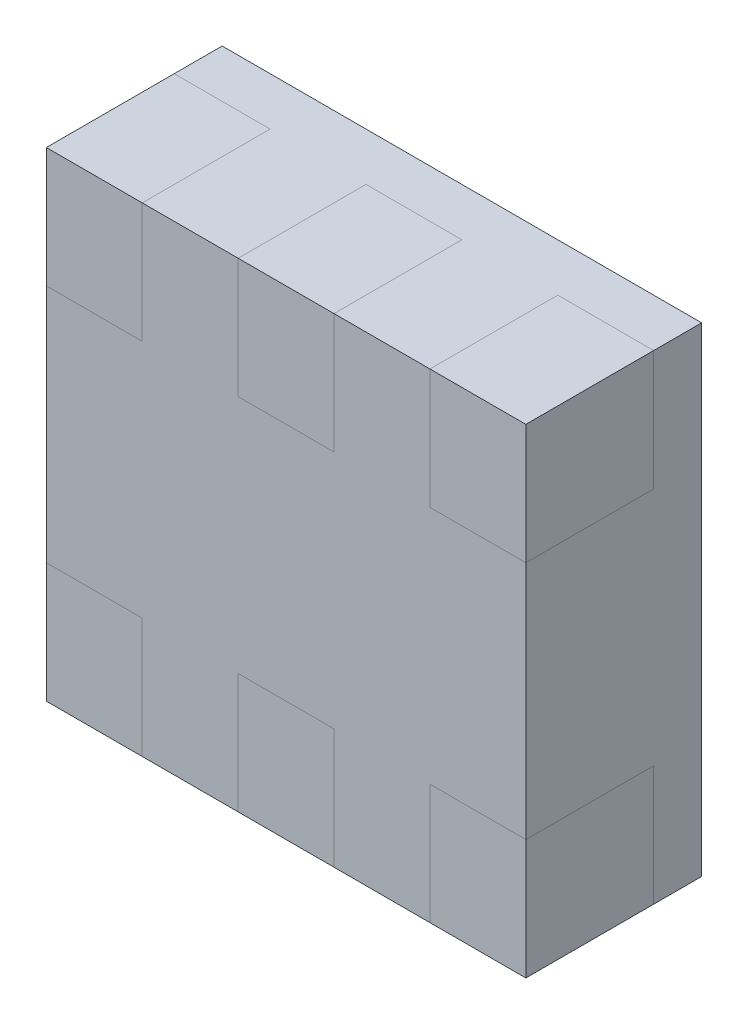
SolidWorks part; units mm, degrees
note: The reader was unsure of these and kept them because the rebuilt part matched: shared geometry of "Sketch2<5>".
ref_plane "Front Plane" through (0, 0, 0) normal (0, 0, 1) x (1, 0, 0)
ref_plane "Top Plane" through (0, 0, 0) normal (0, 1, 0) x (1, 0, 0)
ref_plane "Right Plane" through (0, 0, 0) normal (1, 0, 0) x (0, 0, -1)
sketch "Sketch1" plane through (0, 0, 0) normal (0, 0, 1) x (1, 0, 0)
  line L1 (-1.5, 1.5) -> (1.5, 1.5)
  line L2 (-1.5, 1.5) -> (-1.5, -1.5)
  line L3 (-1.5, -1.5) -> (1.5, -1.5)
  line L4 (1.5, 1.5) -> (1.5, -1.5)
  line L5 (-1.5, 1.5) -> (1.5, -1.5) construction
  line L6 (-1.5, -1.5) -> (1.5, 1.5) construction
  point P0 (0, 0)
  dimension "D1" = 3
  dimension "D2" = 3
extrude "Boss-Extrude1" add sketch "Sketch1" along normal blind 1.1
sketch "Sketch2" plane through (0, 0, 1.1) normal (0, 0, 1) x (1, 0, 0)
  line L0 (1.5, 1.5) -> (-1.5, 1.5) construction
  line L1 (-0.3, 1.5) -> (0.3, 1.5)
  line L2 (-0.3, 1.5) -> (-0.3, 0.75)
  line L3 (-0.3, 0.75) -> (0.3, 0.75)
  line L4 (0.3, 1.5) -> (0.3, 0.75)
  line L5 (-1.5, -1.5) -> (1.5, -1.5) construction
  line L10 (1.5, 1.5) -> (0.9, 1.5)
  line L11 (1.5, 1.5) -> (1.5, 0.75)
  line L12 (1.5, 0.75) -> (0.9, 0.75)
  line L13 (0.9, 1.5) -> (0.9, 0.75)
  line L14 (1.5, -1.5) -> (0.9, -1.5)
  line L15 (1.5, -1.5) -> (1.5, -0.75)
  line L16 (1.5, -0.75) -> (0.9, -0.75)
  line L17 (0.9, -1.5) -> (0.9, -0.75)
  line L18 (-1.5, -1.5) -> (-0.9, -1.5)
  line L19 (-1.5, -1.5) -> (-1.5, -0.75)
  line L20 (-1.5, -0.75) -> (-0.9, -0.75)
  line L21 (-0.9, -1.5) -> (-0.9, -0.75)
  line L22 (-0.3, -1.5) -> (0.3, -1.5)
  line L23 (-0.3, -1.5) -> (-0.3, -0.75)
  line L24 (-0.3, -0.75) -> (0.3, -0.75)
  line L25 (0.3, -1.5) -> (0.3, -0.75)
  line L26 (-1.5, 1.5) -> (-1.5, -1.5) construction
  line L27 (-0.9, 1.5) -> (-1.5, 1.5)
  line L28 (-0.9, 1.5) -> (-0.9, 0.75)
  line L29 (-0.9, 0.75) -> (-1.5, 0.75)
  line L30 (-1.5, 1.5) -> (-1.5, 0.75)
  point P6 (0, 0.75)
  point P34 (0, -0.75)
  dimension "D1" = 0.6
  dimension "D2" = 0.6
  dimension "D3" = 1.5
  dimension "D4" = 1.5
  dimension "D5" = 1.8
  dimension "D6" = 0.6
  dimension "D7" = 0.75
  dimension "D8" = 0.6
extrude "Cut-Extrude1" cut sketch "Sketch2" against normal blind 0.8 contours L29 L30 L27 L28
extrude "Boss-Extrude3" add sketch "Sketch2<5>" against normal up to next separate body contours L1 L4 L3 L2
sketch "Sketch2<5>" plane through (0, 0, 1.1) normal (0, 0, 1) x (1, 0, 0) same geometry as "Sketch2"
